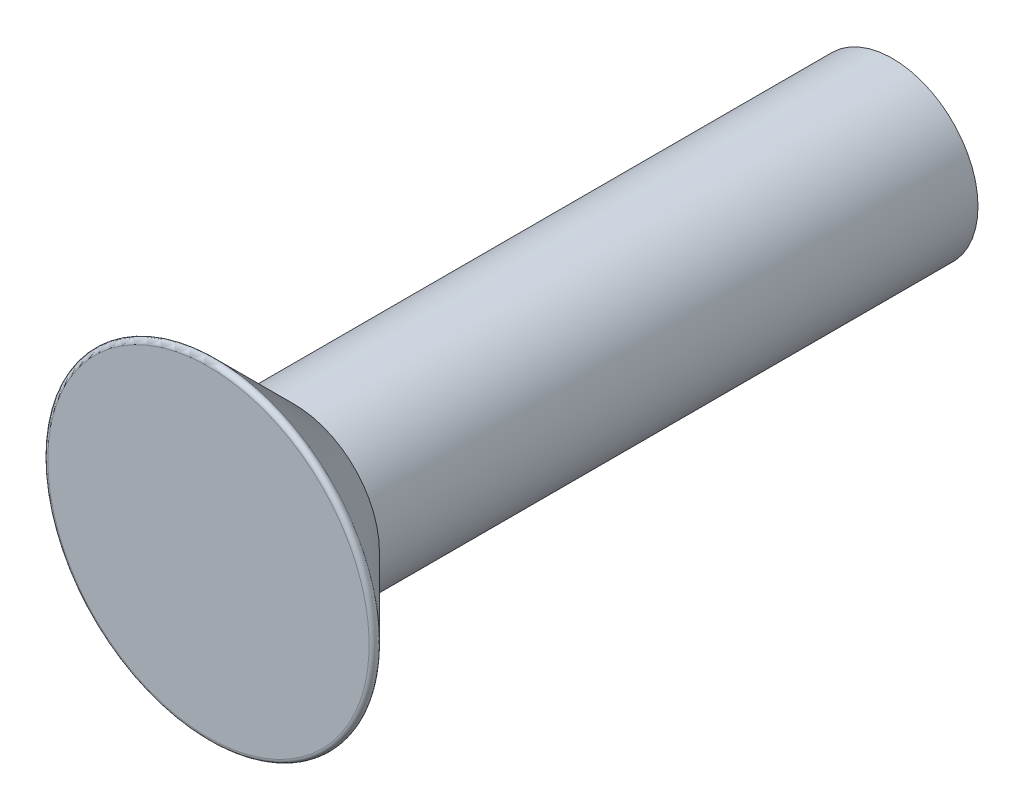
SolidWorks part; units mm, degrees
ref_plane "Front Plane" through (0, 0, 0) normal (0, 0, 1) x (1, 0, 0)
ref_plane "Top Plane" through (0, 0, 0) normal (0, 1, 0) x (1, 0, 0)
ref_plane "Right Plane" through (0, 0, 0) normal (1, 0, 0) x (0, 0, -1)
sketch "BaseBodySke" plane through (0, 0, 0) normal (0, 1, 0) x (1, 0, 0)
  line L0 (0, 0) -> (-6.35, 0)
  line L1 (0, 0) -> (0, 32.7778) construction
  line L2 (0, 0) -> (0, 25.4)
  line L3 (0, 25.4) -> (-3.175, 25.4)
  line L4 (-3.175, 3.175) -> (-3.175, 25.4)
  line L5 (-6.35, 25.4) -> (-6.35, 0) construction
  line L6 (-6.35, -3.175) -> (-6.35, 0) construction
  line L7 (-6.35, 0) -> (-3.175, 3.175)
  line L9 (-3.175, 3.175) -> (-3.175, 0) construction
  dimension "Head_Diameter" = 12.7
  dimension "Diameter" = 6.35
revolve "BaseBody" add sketch "BaseBodySke" angle 360 about L1
fillet "Fillet" radius 0.1588 1 edges at (6.35, 0, 0)
equation "\"D1@Fillet\" = \"Diameter@BaseBodySke\" / 40"
